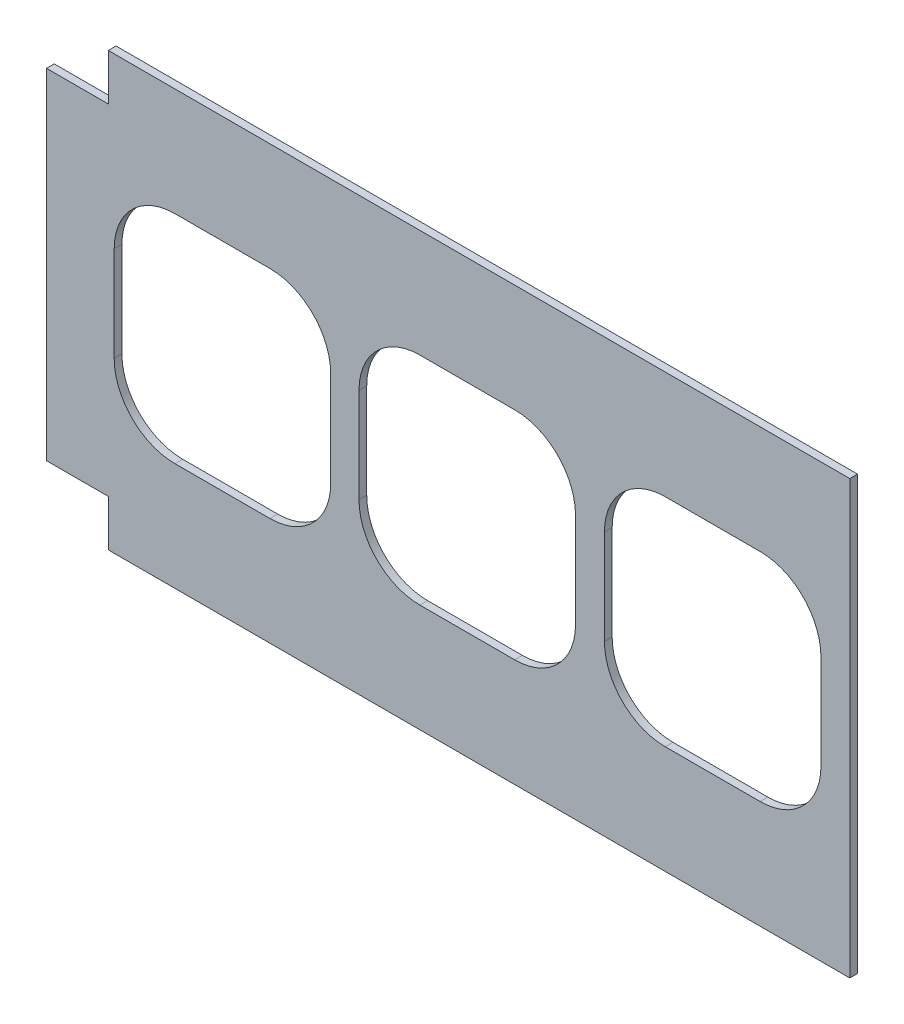
SolidWorks part; units mm, degrees
material "Chrome Stainless Steel"
ref_plane "Front Plane" through (0, 0, 0) normal (0, 0, 1) x (1, 0, 0)
ref_plane "Top Plane" through (0, 0, 0) normal (0, 1, 0) x (1, 0, 0)
ref_plane "Right Plane" through (0, 0, 0) normal (1, 0, 0) x (0, 0, -1)
sketch "Sketch1" plane through (0, 0, 0) normal (0, 0, 1) x (1, 0, 0)
  line L1 (-152.4, -88.9) -> (152.4, -88.9)
  line L3 (-152.4, 88.9) -> (152.4, 88.9)
  line L4 (152.4, -88.9) -> (152.4, 88.9)
  line L5 (-152.4, -88.9) -> (152.4, 88.9) construction
  line L6 (-152.4, 88.9) -> (152.4, -88.9) construction
  line L7 (51.55, -44.5) -> (140.55, -44.5)
  line L8 (51.55, -44.5) -> (51.55, 44.5)
  line L9 (51.55, 44.5) -> (140.55, 44.5)
  line L10 (140.55, -44.5) -> (140.55, 44.5)
  line L11 (51.55, -44.5) -> (140.55, 44.5) construction
  line L12 (51.55, 44.5) -> (140.55, -44.5) construction
  line L13 (-60.974, -44.5) -> (-149.974, -44.5)
  line L14 (-60.974, -44.5) -> (-60.974, 44.5)
  line L15 (-60.974, 44.5) -> (-149.974, 44.5)
  line L16 (-149.974, -44.5) -> (-149.974, 44.5)
  line L17 (-60.974, -44.5) -> (-149.974, 44.5) construction
  line L18 (-60.974, 44.5) -> (-149.974, -44.5) construction
  line L19 (39.661, -44.5) -> (-49.339, -44.5)
  line L20 (39.661, -44.5) -> (39.661, 44.5)
  line L21 (39.661, 44.5) -> (-49.339, 44.5)
  line L22 (-49.339, -44.5) -> (-49.339, 44.5)
  line L23 (39.661, -44.5) -> (-49.339, 44.5) construction
  line L24 (39.661, 44.5) -> (-49.339, -44.5) construction
  line L30 (-152.4, 88.9) -> (-152.4, 69.85)
  line L31 (-152.4, 69.85) -> (-177.8, 69.85)
  line L32 (-177.8, 69.85) -> (-177.8, -69.85)
  line L33 (-177.8, -69.85) -> (-152.4, -69.85)
  line L34 (-152.4, -69.85) -> (-152.4, -88.9)
  point P0 (0, 0)
  point P6 (96.05, 0)
  point P11 (-105.474, 0)
  point P18 (-4.839, 0)
  dimension "D1" = 177.8
  dimension "D2" = 304.8
  dimension "D3" = 89
extrude "Boss-Extrude1" add sketch "Sketch1" along normal blind 3.175
fillet "Fillet1" radius 25 12 edges at (140.55, -44.5, 1.5875) (51.55, -44.5, 1.5875) (51.55, 44.5, 1.5875) (140.55, 44.5, 1.5875) (-149.974, 44.5, 1.5875) (-149.974, -44.5, 1.5875) (-60.974, -44.5, 1.5875) (-60.974, 44.5, 1.5875) (-49.339, 44.5, 1.5875) (39.661, 44.5, 1.5875) (39.661, -44.5, 1.5875) (-49.339, -44.5, 1.5875)
